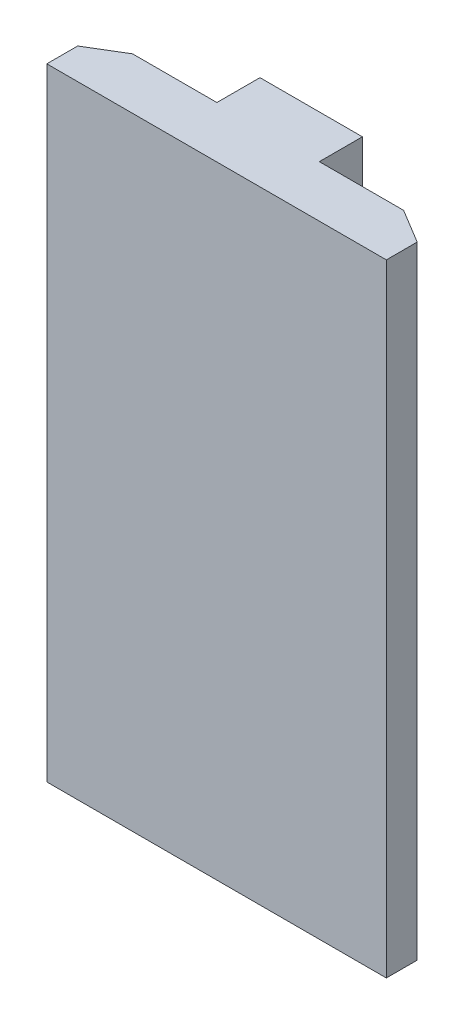
SolidWorks part; units mm, degrees
ref_plane "Front Plane" through (0, 0, 0) normal (0, 0, 1) x (1, 0, 0)
ref_plane "Top Plane" through (0, 0, 0) normal (0, 1, 0) x (1, 0, 0)
ref_plane "Right Plane" through (0, 0, 0) normal (1, 0, 0) x (0, 0, -1)
sketch "housing sketch" plane through (0, 0, 0) normal (0, 1, 0) x (1, 0, 0)
  line L0 (165.1, 0) -> (165.1, 30)
  line L1 (165.1, 30) -> (131.7953, 50.1)
  line L2 (131.7953, 50.1) -> (49.8, 50.1)
  line L3 (49.8, 50.1) -> (49.8, 92)
  line L4 (49.8, 92) -> (-49.8, 92)
  line L5 (-49.8, 92) -> (-49.8, 50.1)
  line L6 (-49.8, 50.1) -> (-131.7953, 50.1)
  line L7 (-131.7953, 50.1) -> (-165.1, 30)
  line L8 (-165.1, 30) -> (-165.1, 0)
  line L9 (-165.1, 0) -> (165.1, 0)
extrude "housing" add sketch "housing sketch" along normal mid plane 604.8
equation "\"diffL\" = 608.8mm"
equation "\"diffW\" = 329.4mm"
equation "\"diffT\" = 2.9mm"
equation "\"chanSlotW\" = 12.9mm"
equation "\"chanSlotDepth\" = 11.13mm"
equation "\"chanFloor\" = 1.57mm"
equation "\"chanLeg\" = 12.7mm"
equation "\"lightL\" = 604.8mm"
equation "\"lightW\" = 330.2mm"
equation "\"lightH\" = 92mm"
equation "\"lightSideFlat\" = 30mm"
equation "\"lightSlopeLen\" = 38.9mm"
equation "\"lightWingDepth\" = 50.1mm"
equation "\"lightWingFlat\" = 90.2mm"
equation "\"lightChanW\" = 99.6mm"
equation "\"lightChanStand\" = 44.1mm"
equation "\"insFlangeD\" = 12.3mm"
equation "\"insFromEnd\" = 20.7mm"
equation "\"insUpSlope\" = 20.8mm"
equation "\"gaugeH\" = 10mm"
equation "\"gaugeStepLen\" = 14mm"
equation "\"gaugeStepW0\" = 13.1mm"
equation "\"gaugeStepDW\" = 0.2mm"
equation "\"gaugeSteps\" = 5mm"
equation "\"gaugeHandleLen\" = 30mm"
equation "\"gaugeHandleW\" = 24mm"
equation "\"gaugeSlot0\" = 3mm"
equation "\"gaugeSlotD\" = 0.1mm"
equation "\"gaugeSlotDepth\" = 8mm"
equation "\"gap\" = 25.4mm"
equation "\"edgeL\" = 1mm"
equation "\"edgeW\" = 0.75mm"
equation "\"proud\" = 2.5mm"
equation "\"seatClr\" = 0.15mm"
equation "\"tongueClrZ\" = 0.1mm"
equation "\"tongueClrX\" = 0.25mm"
equation "\"tongueLen\" = 30mm"
equation "\"armSide\" = 45mm"
equation "\"armEnd\" = 20mm"
equation "\"brkW\" = 26mm"
equation "\"brkT\" = 7mm"
equation "\"brkSeatClr\" = 0.3mm"
equation "\"brkScrewSpan\" = 16mm"
equation "\"pilotD\" = 2.7mm"
equation "\"pilotDepth\" = 10mm"
equation "\"screwClrD\" = 3.9mm"
equation "\"jogBelow\" = 4mm"
equation "\"padT\" = 7mm"
equation "\"padLen\" = 36mm"
equation "\"m6Clr\" = 9mm"
equation "\"m6Slot\" = 5mm"
equation "\"flangeRelD\" = 18mm"
equation "\"flangeRelDepth\" = 1.5mm"
equation "\"relLen\" = 5mm"
equation "\"relDepth\" = 3.3mm"
equation "\"knockN\" = 100mm"
equation "\"petgcfE\" = 3000mm"
equation "\"mockExtent\" = 110mm"
equation "\"relZnear\" = 9.4mm"
equation "\"relZfar\" = 23.4mm"
equation "\"headD\" = 8mm"
equation "\"headH\" = 2.5mm"
equation "\"headFromEnd\" = 6.8mm"
equation "\"headBack\" = 16.4mm"
equation "\"sideClr\" = 0.4mm"
equation "\"cornerRelR\" = 1.5mm"
equation "\"cornerRelBack\" = 0.6mm"
equation "\"endHeadH\" = 2.8mm"
equation "\"footClr\" = 1.2mm"
equation "\"footEndClr\" = 3.5mm"
equation "\"footLift\" = 6mm"
equation "\"footBlockClr\" = 0.5mm"
equation "\"footBack\" = 50mm"
equation "\"footFwd\" = 10mm"
equation "\"footBraceEnd\" = 3mm"
equation "\"footLoadN\" = 25mm"
equation "\"spacerLen\" = 60mm"
equation "\"spacerShort\" = 0.5mm"
equation "\"spacerCham\" = 0.8mm"
equation "\"spacerPerSide\" = 3mm"
equation "\"spacerPerEnd\" = 1mm"
equation "\"toolR\" = 9mm"
equation "\"visR\" = 4mm"
equation "\"edgeR\" = 1mm"
equation "\"bendOutR\" = 5mm"
equation "\"insideR\" = 2.5mm"
equation "\"footCornerR\" = 10mm"
equation "\"footFrontR\" = 8mm"
equation "\"braceKinkR\" = 12mm"
equation "\"bedCham\" = 1mm"
equation "\"bedChamSmall\" = 0.6mm"
equation "\"soleTopR\" = 2mm"
equation "\"cornerR\" = 6mm"
equation "\"rimInR\" = 1mm"
equation "\"insFlangeH\" = 1mm"
